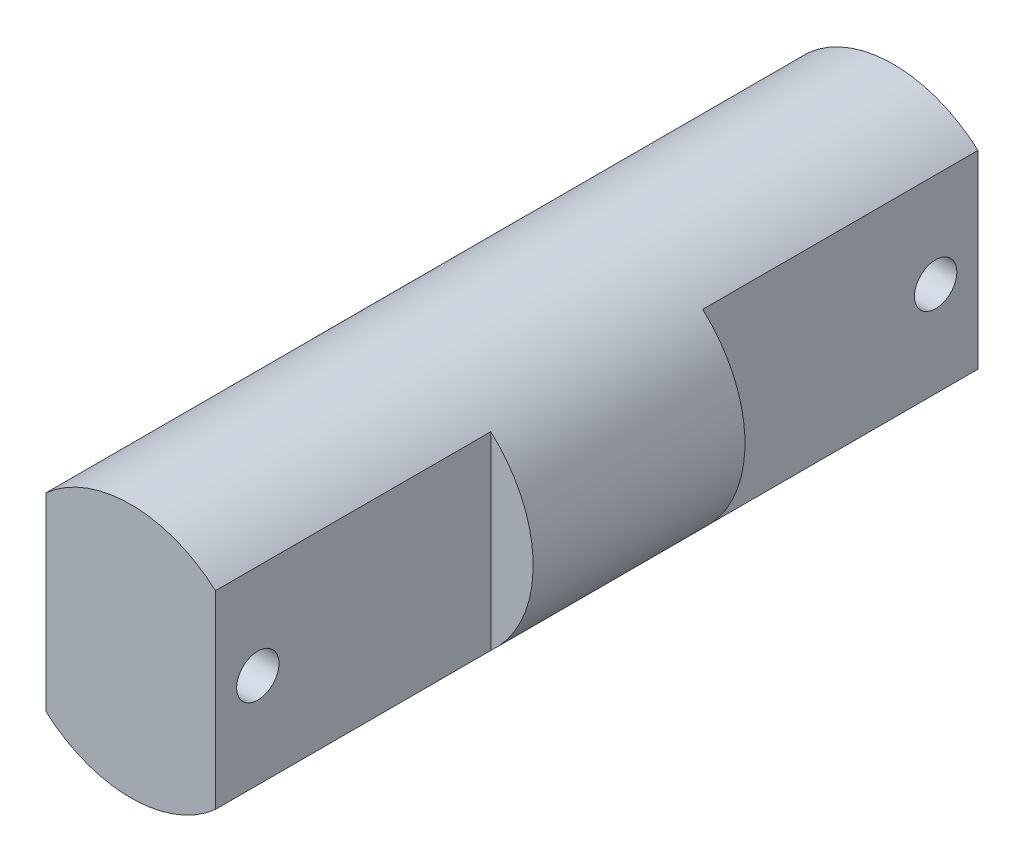
SolidWorks part; units mm, degrees
ref_plane "Front Plane" through (0, 0, 0) normal (0, 0, 1) x (1, 0, 0)
ref_plane "Top Plane" through (0, 0, 0) normal (0, 1, 0) x (1, 0, 0)
ref_plane "Right Plane" through (0, 0, 0) normal (1, 0, 0) x (0, 0, -1)
sketch "Sketch2" plane through (0, 0, 0) normal (0, 0, 1) x (1, 0, 0)
  circle A0 centre (0, 0) radius 38.1
  dimension "D1" = 76.2
extrude "Boss-Extrude1" add sketch "Sketch2" against normal blind 228.6
sketch "Sketch3" plane through (0, 0, 0) normal (1, 0, 0) x (0, 0, -1)
  line L0 (228.6, 38.1) -> (0, 38.1) construction
  line L1 (-82.55, -38.1) -> (82.55, -38.1)
  line L2 (-82.55, -38.1) -> (-82.55, 38.1)
  line L3 (-82.55, 38.1) -> (82.55, 38.1)
  line L4 (82.55, -38.1) -> (82.55, 38.1)
  line L5 (-82.55, -38.1) -> (82.55, 38.1) construction
  line L6 (-82.55, 38.1) -> (82.55, -38.1) construction
  point P0 (0, 0)
  dimension "D1" = 165.1
extrude "Cut-Extrude1" cut sketch "Sketch3" along normal blind 25.4 from offset 25.4
extrude "Cut-Extrude2" cut sketch "Sketch3<2>" against normal blind 25.4 from offset 25.4 offset against normal yes
sketch "Sketch3<2>" plane through (0, 0, 0) normal (1, 0, 0) x (0, 0, -1) same geometry as "Sketch3"
sketch "Sketch4" plane through (25.4, 0, 0) normal (1, 0, 0) x (0, 0, -1)
  circle A0 centre (12.7, 0) radius 6.35
  point P2 (0, 0)
  point P4 (12.7, 0)
  dimension "D1" = 12.7
  dimension "D2" = 12.7
extrude "Cut-Extrude3" cut sketch "Sketch4" against normal up to next
sketch "Sketch5" plane through (0, 0, 0) normal (1, 0, 0) x (0, 0, -1)
  line L0 (114.3, -38.1) -> (114.3, 38.1) construction
  line L1 (228.6, 38.1) -> (0, 38.1) construction
  line L2 (0, -38.1) -> (228.6, -38.1) construction
  point P4 (114.3, -38.1)
ref_plane "Plane1" through (0, 0, -114.3) normal (0, 0, 1) x (1, 0, 0)
mirror "Mirror1" about plane through (0, 0, -114.3) normal (0, 0, 1) of "Cut-Extrude3", "Cut-Extrude1", "Cut-Extrude2"
